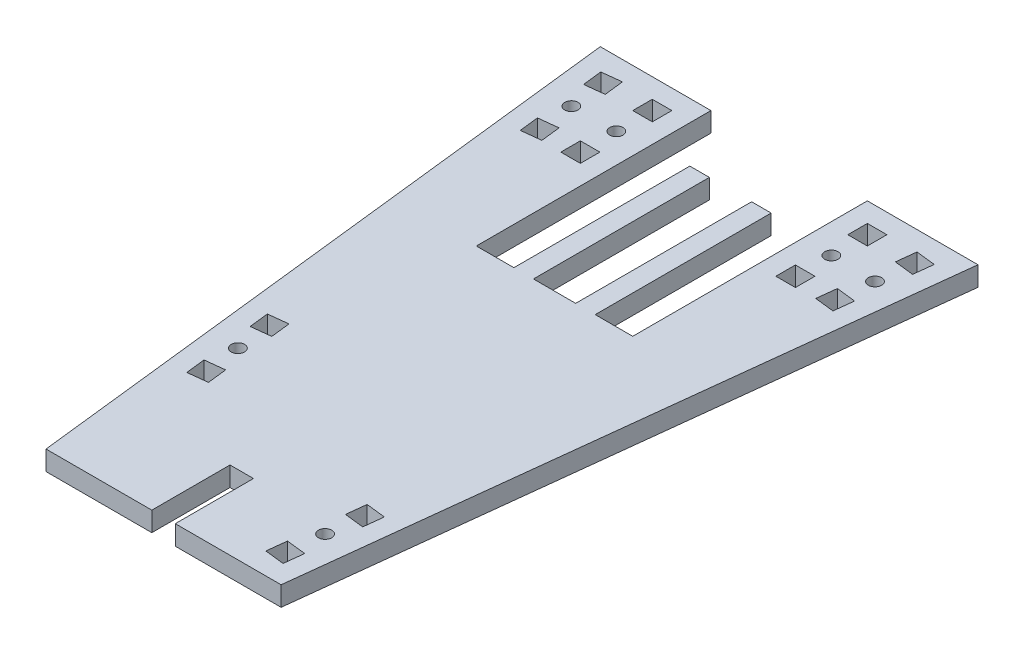
SolidWorks part; units mm, degrees
ref_plane "Front Plane" through (0, 0, 0) normal (0, 0, 1) x (1, 0, 0)
ref_plane "Top Plane" through (0, 0, 0) normal (0, 1, 0) x (1, 0, 0)
ref_plane "Right Plane" through (0, 0, 0) normal (1, 0, 0) x (0, 0, -1)
sketch "Sketch1" plane through (0, 0, 0) normal (0, 1, 0) x (1, 0, 0)
  line L0 (0, 0) -> (0, -183.008) construction
  line L1 (-48.5611, 76.2) -> (-25.4, 76.2)
  line L2 (48.5611, 76.2) -> (25.4, -127) construction
  line L3 (-48.5611, 76.2) -> (-25.4, -127) construction
  line L4 (38.1, 40.132) -> (44.45, 40.132) construction
  line L5 (-48.5611, 76.2) -> (-61.3433, 76.2)
  line L6 (-3.81, -127) -> (-3.81, -101.6)
  line L7 (-57.15, 0) -> (57.15, 0) construction
  line L8 (31.75, 76.2) -> (31.75, 40.132) construction
  line L9 (-31.75, 76.2) -> (-31.75, 40.132) construction
  line L10 (6.858, 57.15) -> (6.858, 0) construction
  line L11 (-6.858, 57.15) -> (-6.858, 0) construction
  line L12 (-6.858, 57.15) -> (-6.858, 0)
  line L13 (-6.858, 0) -> (6.858, 0)
  line L14 (6.858, 0) -> (6.858, 57.15)
  line L15 (6.858, 57.15) -> (13.208, 57.15)
  line L16 (-3.81, -101.6) -> (3.81, -101.6)
  line L17 (3.81, -127) -> (3.81, -101.6)
  line L18 (13.208, 57.15) -> (13.208, 0)
  line L19 (13.208, 0) -> (25.4, 0)
  line L20 (25.4, 0) -> (25.4, 76.2)
  line L21 (25.4, 76.2) -> (48.5611, 76.2)
  line L22 (-25.4, 0) -> (-25.4, 76.2)
  line L23 (-13.208, 0) -> (-25.4, 0)
  line L24 (-13.208, 57.15) -> (-13.208, 0)
  line L25 (-6.858, 0) -> (-6.858, 57.15)
  line L26 (-13.208, 57.15) -> (-6.858, 57.15)
  line L27 (-3.81, -127) -> (3.81, -101.6) construction
  line L28 (-3.81, -101.6) -> (3.81, -127) construction
  line L29 (48.5611, 76.2) -> (61.3433, 76.2)
  line L30 (61.3433, 76.2) -> (38.1822, -127)
  line L31 (-25.4, -127) -> (-3.81, -127)
  line L32 (3.81, -127) -> (25.4, -127)
  line L33 (25.4, -127) -> (38.1822, -127)
  line L34 (-61.3433, 76.2) -> (-38.1822, -127)
  line L35 (-25.4, -127) -> (-38.1822, -127)
  line L36 (-36.1338, -88.9) -> (-29.8247, -88.1809) construction
  line L37 (31.7911, -127) -> (25.482, -126.2809) construction
  line L38 (32.5102, -120.6909) -> (31.7911, -127) construction
  line L39 (-36.8529, -82.5909) -> (-36.1338, -88.9) construction
  point P0 (0, 0)
  point P15 (0, -114.3)
  line B0 (34.925, 40.132) -> (34.925, 69.85) construction
  line B1 (32.766, 54.991) -> (37.084, 54.991) construction
  line B2 (31.75, 63.5) -> (38.1, 63.5)
  line B3 (31.75, 63.5) -> (31.75, 69.85)
  line B4 (31.75, 69.85) -> (38.1, 69.85)
  line B5 (38.1, 63.5) -> (38.1, 69.85)
  line B6 (31.75, 63.5) -> (38.1, 69.85) construction
  line B7 (31.75, 69.85) -> (38.1, 63.5) construction
  line B8 (31.75, 40.132) -> (38.1, 46.482) construction
  line B9 (31.75, 46.482) -> (38.1, 40.132) construction
  line B10 (38.1, 46.482) -> (38.1, 40.132)
  line B11 (31.75, 40.132) -> (38.1, 40.132)
  line B12 (31.75, 46.482) -> (31.75, 40.132)
  line B13 (31.75, 46.482) -> (38.1, 46.482)
  circle B14 centre (34.925, 54.991) radius 2.159
  line B15 (-34.925, 40.132) -> (-34.925, 69.85) construction
  line B16 (-32.766, 54.991) -> (-37.084, 54.991) construction
  line B17 (-31.75, 63.5) -> (-38.1, 63.5)
  line B18 (-31.75, 63.5) -> (-31.75, 69.85)
  line B19 (-31.75, 69.85) -> (-38.1, 69.85)
  line B20 (-38.1, 63.5) -> (-38.1, 69.85)
  line B21 (-31.75, 63.5) -> (-38.1, 69.85) construction
  line B22 (-31.75, 69.85) -> (-38.1, 63.5) construction
  line B23 (-31.75, 40.132) -> (-38.1, 46.482) construction
  line B24 (-31.75, 46.482) -> (-38.1, 40.132) construction
  line B25 (-38.1, 46.482) -> (-38.1, 40.132)
  line B26 (-31.75, 40.132) -> (-38.1, 40.132)
  line B27 (-31.75, 46.482) -> (-31.75, 40.132)
  line B28 (-31.75, 46.482) -> (-38.1, 46.482)
  circle B29 centre (-34.925, 54.991) radius 2.159
  line B30 (47.631, 40.0045) -> (50.9965, 69.5313) construction
  line B31 (47.1687, 55.0124) -> (51.4589, 54.5234) construction
  line B32 (47.1228, 63.5817) -> (53.432, 62.8626)
  line B33 (47.1228, 63.5817) -> (47.842, 69.8909)
  line B34 (47.842, 69.8909) -> (54.1511, 69.1717)
  line B35 (53.432, 62.8626) -> (54.1511, 69.1717)
  line B36 (47.1228, 63.5817) -> (54.1511, 69.1717) construction
  line B37 (47.842, 69.8909) -> (53.432, 62.8626) construction
  line B38 (44.4764, 40.364) -> (51.5047, 45.9541) construction
  line B39 (45.1956, 46.6732) -> (50.7856, 39.6449) construction
  line B40 (51.5047, 45.9541) -> (50.7856, 39.6449)
  line B41 (44.4764, 40.364) -> (50.7856, 39.6449)
  line B42 (45.1956, 46.6732) -> (44.4764, 40.364)
  line B43 (45.1956, 46.6732) -> (51.5047, 45.9541)
  circle B44 centre (49.3138, 54.7679) radius 2.159
  line B45 (29.3557, -120.3313) -> (32.7212, -90.8045) construction
  line B46 (28.8933, -105.3234) -> (33.1835, -105.8124) construction
  line B47 (28.8475, -96.7541) -> (35.1566, -97.4732)
  line B48 (28.8475, -96.7541) -> (29.5666, -90.4449)
  line B49 (29.5666, -90.4449) -> (35.8758, -91.164)
  line B50 (35.1566, -97.4732) -> (35.8758, -91.164)
  line B51 (28.8475, -96.7541) -> (35.8758, -91.164) construction
  line B52 (29.5666, -90.4449) -> (35.1566, -97.4732) construction
  line B53 (26.2011, -119.9717) -> (33.2294, -114.3817) construction
  line B54 (26.9202, -113.6626) -> (32.5102, -120.6909) construction
  line B55 (33.2294, -114.3817) -> (32.5102, -120.6909)
  line B56 (26.2011, -119.9717) -> (32.5102, -120.6909)
  line B57 (26.9202, -113.6626) -> (26.2011, -119.9717)
  line B58 (26.9202, -113.6626) -> (33.2294, -114.3817)
  circle B59 centre (31.0384, -105.5679) radius 2.159
  line B60 (-33.6984, -82.2313) -> (-37.0639, -52.7045) construction
  line B61 (-33.236, -67.2234) -> (-37.5262, -67.7124) construction
  line B62 (-33.1902, -58.6541) -> (-39.4993, -59.3732)
  line B63 (-33.1902, -58.6541) -> (-33.9093, -52.3449)
  line B64 (-33.9093, -52.3449) -> (-40.2185, -53.064)
  line B65 (-39.4993, -59.3732) -> (-40.2185, -53.064)
  line B66 (-33.1902, -58.6541) -> (-40.2185, -53.064) construction
  line B67 (-33.9093, -52.3449) -> (-39.4993, -59.3732) construction
  line B68 (-30.5438, -81.8717) -> (-37.5721, -76.2817) construction
  line B69 (-31.2629, -75.5626) -> (-36.8529, -82.5909) construction
  line B70 (-37.5721, -76.2817) -> (-36.8529, -82.5909)
  line B71 (-30.5438, -81.8717) -> (-36.8529, -82.5909)
  line B72 (-31.2629, -75.5626) -> (-30.5438, -81.8717)
  line B73 (-31.2629, -75.5626) -> (-37.5721, -76.2817)
  circle B74 centre (-35.3811, -67.4679) radius 2.159
  line B75 (-47.631, 40.0045) -> (-50.9965, 69.5313) construction
  line B76 (-47.1687, 55.0124) -> (-51.4589, 54.5234) construction
  line B77 (-47.1228, 63.5817) -> (-53.432, 62.8626)
  line B78 (-47.1228, 63.5817) -> (-47.842, 69.8909)
  line B79 (-47.842, 69.8909) -> (-54.1511, 69.1717)
  line B80 (-53.432, 62.8626) -> (-54.1511, 69.1717)
  line B81 (-47.1228, 63.5817) -> (-54.1511, 69.1717) construction
  line B82 (-47.842, 69.8909) -> (-53.432, 62.8626) construction
  line B83 (-44.4764, 40.364) -> (-51.5047, 45.9541) construction
  line B84 (-45.1956, 46.6732) -> (-50.7856, 39.6449) construction
  line B85 (-51.5047, 45.9541) -> (-50.7856, 39.6449)
  line B86 (-44.4764, 40.364) -> (-50.7856, 39.6449)
  line B87 (-45.1956, 46.6732) -> (-44.4764, 40.364)
  line B88 (-45.1956, 46.6732) -> (-51.5047, 45.9541)
  circle B89 centre (-49.3138, 54.7679) radius 2.159
  dimension "D1" = 63.5
  dimension "D2" = 6.35
  dimension "D3" = 6.858
  dimension "D4" = 50.8
  dimension "D5" = 25.4
  dimension "D6" = 7.62
  dimension "D7" = 19.05
  dimension "D8" = 203.2
  dimension "D9" = 6.35
  dimension "D10" = 6.35
  dimension "D11" = 6.35
  dimension "D12" = 76.2
  dimension "D13" = 6.35
  dimension "D14" = 6.35
  dimension "D15" = 38.1
  dimension "D16" = 127
  dimension "D17" = 93.3092
  dimension "D18" = 131.6559
sketch_block_instance "Female T-Slot Assembly-1"
sketch_block "Female T-Slot Assembly" parameters "D4"=4.318, "D1"=6.35, "D2"=6.35, "D3"=6.35
sketch_block_instance "Female T-Slot Assembly-3"
sketch_block_instance "Female T-Slot Assembly-1"
sketch_block_instance "Female T-Slot Assembly-14"
sketch_block_instance "Female T-Slot Assembly-16"
sketch_block_instance "Female T-Slot Assembly-17"
extrude "Boss-Extrude1" add sketch "Sketch1" along normal blind 6.35 contours L26 L24 L23 L22 L1 L21 L20 L19 L18 L15 L14 L13 L12 B29 B28 B27 B26 B25 B12 B13 B10 B11 B5 B2 B3 region at (0.0254, 0, 28.403)
equation "\"Ball Diameter\"= 1.75in"
equation "\"Ball Radius\" = \"Ball Diameter\"/2"
equation "\"Sheet Thickness\"= 0.25in"
equation "\"Screw Diameter\"= .17in"
equation "\"Robot Diameter\"= 14in"
equation "\"Castor Screw Diameter\"= 0.22in"
equation "\"Wheel Diameter\" = 4in"
equation "\"Nut Diameter\" = 8.4mm"
equation "\"Nut Height\" = 2.9mm"
equation "\"Screw Height\" = 0.55in"
equation "\"Pulley Diameter\" = 1in"
equation "\"Reactor Height\" = 14in"
equation "\"Elevator Height\" = 11.5in"
equation "\"Elevator Width\" = \"Ball Diameter\" + 0.25in"
equation "\"Elevator Bearing Diameter\" = sqr(2*(\"Sheet Thickness\"^2)) + 0.2in"
equation "\"Elevator Axle Endcap Diameter\" = \"Pulley Diameter\" + 0.25in"
equation "\"Elevator Axle Length\" = \"Elevator Width\" + 8*\"Sheet Thickness\""
equation "\"Elevator Clearance from Axis\" = 3.28in"
equation "\"Elevator Horizontal Clearance\" = \"Elevator Width\" + 0.5in"
equation "\"Claw Horizontal Seperation\" = (\"Elevator Width\"/2) - (1.5 * \"Sheet Thickness\") - 0.15in"
equation "\"Claw Radius\" = \"Ball Radius\" + 0.1in"
equation "\"Castor Wheel Height\" = 1.25in"
equation "\"Length of Chute\" = 8in"
equation "\"D4@Sketch1\"=\"Ball Diameter\" + 0.25in"
equation "\"D8@Sketch1\"=\"Length of Chute\""
